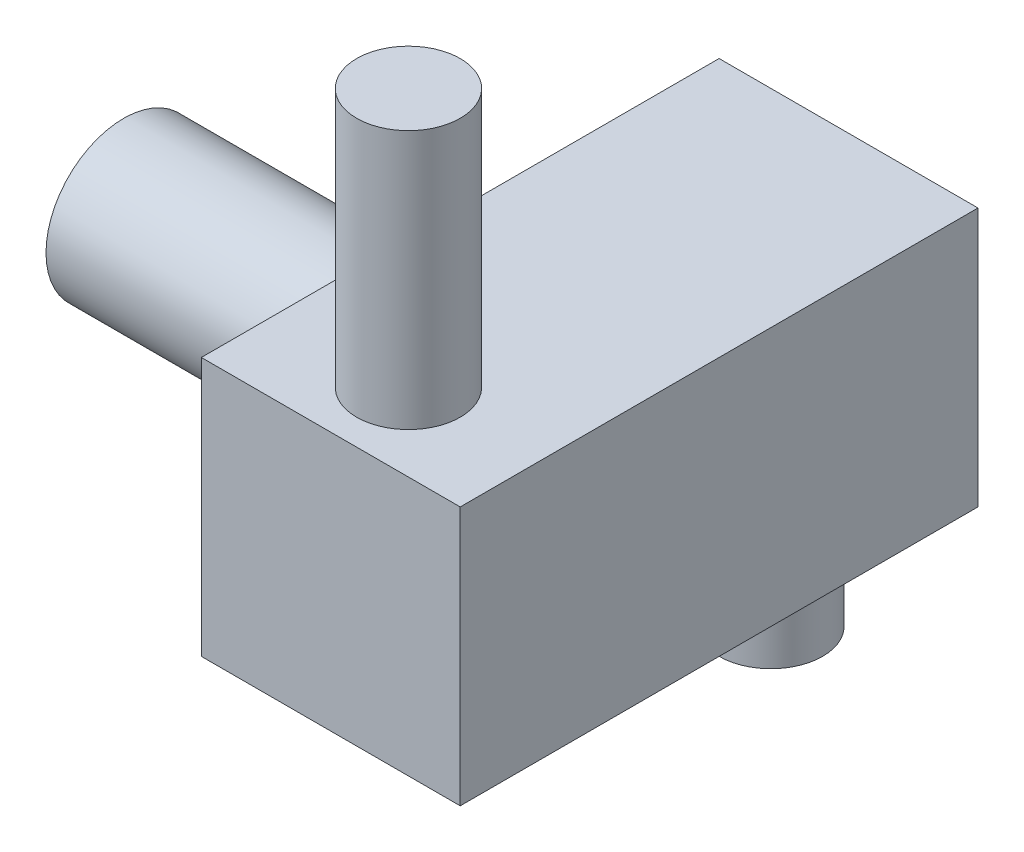
SolidWorks part; units mm, degrees
ref_plane "Front Plane" through (0, 0, 0) normal (0, 0, 1) x (1, 0, 0)
ref_plane "Top Plane" through (0, 0, 0) normal (0, 1, 0) x (1, 0, 0)
ref_plane "Right Plane" through (0, 0, 0) normal (1, 0, 0) x (0, 0, -1)
sketch "Sketch1" plane through (0, 0, 0) normal (0, 1, 0) x (1, 0, 0)
  line L1 (0, 0) -> (5, 0)
  line L2 (0, 0) -> (0, -10)
  line L3 (0, -10) -> (5, -10)
  line L4 (5, 0) -> (5, -10)
  dimension "D1" = 5
  dimension "D2" = 10
extrude "Boss-Extrude1" add sketch "Sketch1" along normal blind 5
sketch "Sketch2" plane through (0, 5, 0) normal (0, 1, 0) x (1, 0, 0)
  line L0 (5, -8.5) -> (0, -8.5) construction
  line L1 (5, -10) -> (5, 0) construction
  line L2 (0, 0) -> (0, -10) construction
  line L3 (2.5, -9.5) -> (2.5, -10) construction
  line L4 (0, -10) -> (5, -10) construction
  circle A0 centre (2.5, -8.5) radius 1
  dimension "D1" = 2
  dimension "D2" = 0.5
extrude "Boss-Extrude2" add sketch "Sketch2" along normal blind 5
sketch "Sketch3" plane through (0, 0, 0) normal (-1, 0, 0) x (0, 0, 1)
  line L1 (5, 1.75) -> (5, 0) construction
  line L4 (0, 0) -> (10, 0) construction
  circle A0 centre (5, 1.75) radius 1.5
  dimension "D1" = 3
  dimension "D2" = 1.75
extrude "Boss-Extrude3" add sketch "Sketch3" along normal blind 6.5
sketch "Sketch4" plane through (0, 0, 0) normal (0, -1, 0) x (1, 0, 0)
  line L0 (2.5, 0.5) -> (2.5, 0) construction
  line L1 (5, 0) -> (0, 0) construction
  line L2 (0, 1.5) -> (5, 1.5) construction
  line L3 (0, 0) -> (0, 10) construction
  line L4 (5, 10) -> (5, 0) construction
  circle A0 centre (2.5, 1.5) radius 1
  dimension "D1" = 2
  dimension "D2" = 0.5
extrude "Boss-Extrude4" add sketch "Sketch4" along normal blind 2.5
fillet "Fillet1" radius 0.75 1 edges at (0, 1.75, 3.5)
